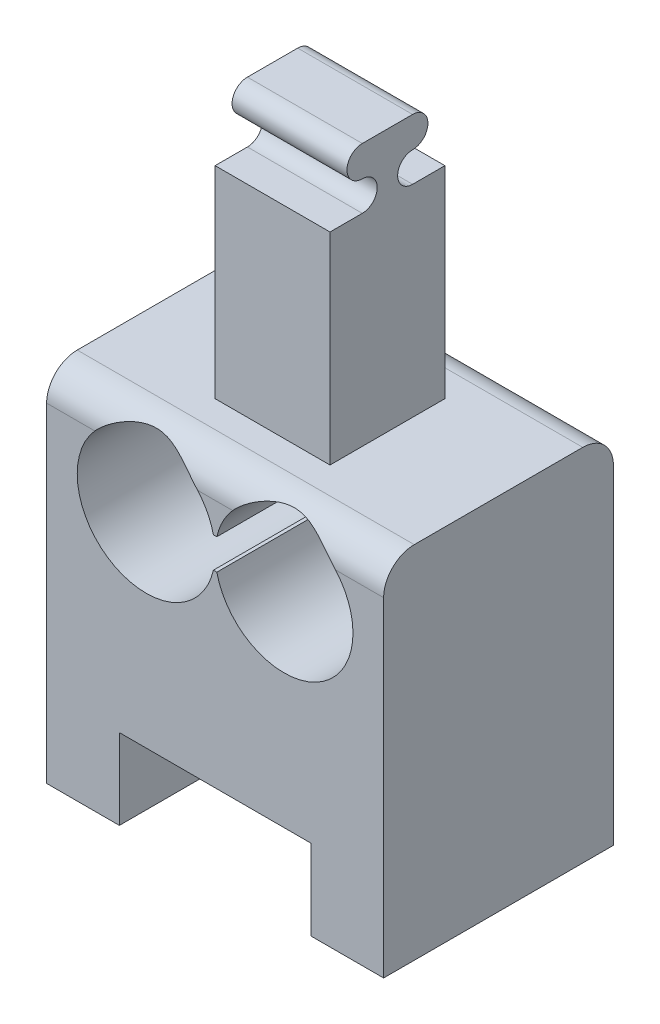
SolidWorks part; units mm, degrees
ref_plane "Front Plane" through (0, 0, 0) normal (0, 0, 1) x (1, 0, 0)
ref_plane "Top Plane" through (0, 0, 0) normal (0, 1, 0) x (1, 0, 0)
ref_plane "Right Plane" through (0, 0, 0) normal (1, 0, 0) x (0, 0, -1)
sketch "Sketch1" plane through (0, 0, 0) normal (0, 0, 1) x (1, 0, 0)
  line L6 (48.0544, -51.8775) -> (48.2794, -51.8775)
  line L19 (51.6669, -45.8775) -> (59.1669, -45.8775)
  line L20 (51.6669, -45.8775) -> (44.6669, -45.8775) construction
  line L21 (41.9169, -64.1275) -> (54.4169, -64.1275)
  line L22 (41.9169, -64.1275) -> (41.9169, -69.3775)
  line L24 (54.4169, -64.1275) -> (54.4169, -69.3775)
  line L25 (59.1669, -69.3775) -> (37.1669, -69.3775)
  line L28 (37.1669, -45.8775) -> (44.6669, -45.8775)
  line L32 (44.6669, -45.8775) -> (51.6669, -45.8775)
  line L33 (37.1669, -45.8775) -> (37.1669, -69.3775)
  line L34 (59.1669, -45.8775) -> (59.1669, -69.3775)
  line L35 (59.1669, -50.8775) -> (37.1669, -50.8775) construction
  line L36 (48.1669, -50.8775) -> (48.1669, 64.3396) construction
  line L38 (48.0544, -49.8775) -> (48.2794, -49.8775)
  arc A0 (48.2794, -51.8775) -> (48.2794, -49.8775) centre (52.6669, -50.8775) ccw
  arc A1 (48.0544, -49.8775) -> (48.0544, -51.8775) centre (43.6669, -50.8775) ccw
  point P0 (0, 0)
  point P9 (51.5, -66.7525)
  point P11 (41.9169, -66.7525)
  dimension "D7" = 9
  dimension "D3" = 12.5
  dimension "D4" = 5
  dimension "D8" = 7.5
  dimension "D9" = 7.5
  dimension "D10" = 23.5
  dimension "D11" = 5.25
  dimension "D12" = 4.75
  dimension "D13" = 9
  dimension "D5" = 22
extrude "pusher base" add sketch "Sketch1" along normal blind 15 contours L32 L28 L19 A1 A0 L21 L24 L22 region at (48.1669, -58.4331, 0)
sketch "Sketch3" plane through (0, -64.1275, 0) normal (0, -1, 0) x (1, 0, 0)
  line L0 (48.1669, 15) -> (48.1669, 0) construction
  line L1 (41.9169, 15) -> (54.4169, 15) construction
  line L2 (41.9169, 0) -> (54.4169, 0) construction
  circle A0 centre (48.1669, 7.5) radius 1.95
  point P10 (48.1669, 7.5)
  dimension "D1" = 3.9
extrude "screw hole" cut sketch "Sketch3" against normal blind 7.5
ref_plane "Plane1" through (0, 0, 7.5) normal (0, 0, 1) x (1, 0, 0)
sketch "Sketch6" plane through (0, 0, 7.5) normal (0, 0, 1) x (1, 0, 0)
  line L0 (41.9169, -64.1275) -> (54.4169, -64.1275) construction
  line L5 (37.1669, -45.8775) -> (59.1669, -45.8775) construction
  line L6 (44.4169, -25.6275) -> (51.9169, -25.6275)
  line L11 (44.4169, -25.6275) -> (44.4169, -45.8775)
  line L12 (44.4169, -45.8775) -> (51.9169, -45.8775)
  line L13 (51.9169, -25.6275) -> (51.9169, -45.8775)
  line L14 (48.1669, -64.1275) -> (48.1669, -27.6275) construction
  line L15 (51.9169, -25.6275) -> (44.4169, -25.6275)
  line L16 (51.9169, -25.6275) -> (51.9169, -15.6275)
  line L17 (51.9169, -15.6275) -> (44.4169, -15.6275)
  line L18 (44.4169, -25.6275) -> (44.4169, -15.6275)
  point P2 (48.1669, -25.6275)
  point P8 (48.1669, -45.8775)
  dimension "D1" = 7.5
  dimension "D3" = 7.5
  dimension "D4" = 10
  dimension "D5" = 38.5
extrude "pusher head" add sketch "Sketch6" along normal mid plane 7.5 contours L18 L15 L6 L16 L17 | L13 L6 L12 | L11 L12 L6 region at (48.1669, -20.6275, 7.5) region at (48.1669, -35.7525, 7.5)
fillet "Fillet1" radius 2 2 edges at (48.1669, -45.8775, 0) (48.1669, -45.8775, 15)
sketch "Sketch12" plane through (44.4169, 0, 0) normal (-1, 0, 0) x (0, 0, 1)
  line L0 (7.5, -15.6275) -> (7.5, -45.8775) construction
  line L1 (11.25, -15.6275) -> (3.75, -15.6275) construction
  line L2 (11.25, -45.8775) -> (3.75, -45.8775) construction
  line L3 (3.75, -30.7525) -> (11.25, -30.7525) construction
  line L4 (3.75, -45.8775) -> (3.75, -15.6275) construction
  line L5 (11.25, -45.8775) -> (11.25, -15.6275) construction
  line L6 (5.8585, -32.7525) -> (3.75, -32.7525)
  line L7 (5.8585, -28.7525) -> (9.1415, -28.7525)
  line L8 (9.1415, -32.7525) -> (11.25, -32.7525)
  line L9 (3.75, -32.7025) -> (5.8585, -32.7025)
  line L10 (11.25, -32.7025) -> (9.1415, -32.7025)
  arc A0 (5.8585, -32.7525) -> (5.8585, -30.7525) centre (5.8585, -31.7525) ccw
  arc A1 (5.8585, -28.7525) -> (5.8585, -30.7525) centre (5.8585, -29.7525) ccw
  arc A2 (9.1415, -32.7525) -> (9.1415, -30.7525) centre (9.1415, -31.7525) cw
  arc A3 (9.1415, -28.7525) -> (9.1415, -30.7525) centre (9.1415, -29.7525) cw
  arc A4 (5.8585, -30.7525) -> (5.8585, -32.7025) centre (5.8585, -31.7275) cw
  arc A5 (9.1415, -30.7525) -> (9.1415, -32.7025) centre (9.1415, -31.7275) ccw
  arc A6 (5.8585, -30.7525) -> (5.8585, -28.7525) centre (5.9027, -29.7525) cw
  arc A7 (9.1415, -30.7525) -> (9.1415, -28.7525) centre (9.0973, -29.7525) ccw
  point P25 (7.5, -28.7525)
  line M4 (3.75, -15.6275) -> (3.75, -45.8775)
  line M6 (11.25, -45.8775) -> (11.25, -15.6275)
  line M7 (11.25, -15.6275) -> (3.75, -15.6275)
  dimension "D1" = 2
  dimension "D2" = 0.05
extrude "Cut-Extrude1" cut sketch "Sketch12" against normal blind 7.5 contours A3 A5 L10 L9 A4 A1 L7 M6 M7 M4 region at (44.4169, -23.4683, 7.5)
equation "\"PusherHeight\"=2"
equation "\"PusherWidth\"=11"
equation "\"PusherLongWidth\"=5"
equation "\"RodDiameter\"=0.5"
equation "\"HookLength\"=2.01152"
equation "\"HookHeight\"=0.999652"
equation "\"HookInnerLength\"=2"
equation "\"RodHeightDistance\"=0.4276"
equation "\"RodWidthDistance\"=0.75"
equation "\"PusherDepth\"=2"
equation "\"BuckleShaftDiameter\"=0.383646"
equation "\"BeltBuckleDistance\"=1.5"
equation "\"DowelDiameter\"=0.9"
equation "\"D7@Sketch1\"=\"DowelDiameter\""
equation "\"RodSeperationDistance\"=3.98"
equation "\"BuckleNutDiameter\"=0.39"
equation "\"D1@Sketch3\"=\"BuckleNutDiameter\""
equation "\"belt hole width\"=1.4"
equation "\"pusher height\"=3.5175"
equation "\"pusher slot width\"=0.75"
equation "\"D1@Sketch6\"=\"pusher slot width\""
equation "\"pushing bar width\"=1"
equation "\"D4@Sketch6\"=\"pushing bar width\""
equation "\"doweltotop\"=0.5"
equation "\"D4@Sketch1\"=\"doweltotop\""
equation "\"dowel separation\"=0.9"
equation "\"D13@Sketch1\"=\"dowel separation\""
